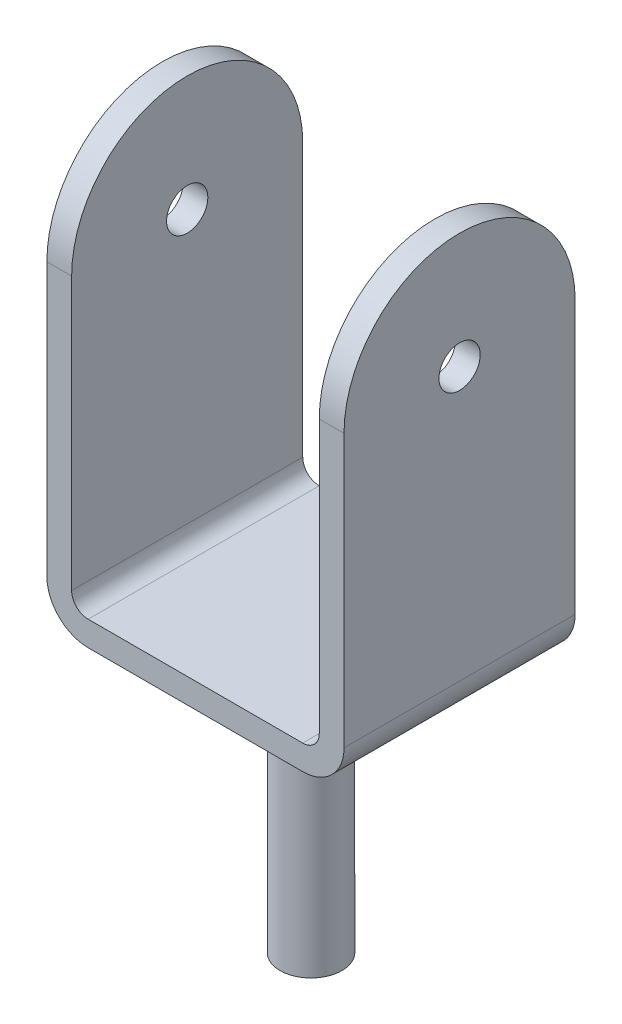
SolidWorks part; units mm, degrees
ref_plane "Front Plane" through (0, 0, 0) normal (0, 0, 1) x (1, 0, 0)
ref_plane "Top Plane" through (0, 0, 0) normal (0, 1, 0) x (1, 0, 0)
ref_plane "Right Plane" through (0, 0, 0) normal (1, 0, 0) x (0, 0, -1)
sketch "Sketch4" plane through (0, 0, 0) normal (0, 0, 1) x (1, 0, 0)
  line L0 (0, 0) -> (0, 149.0261) construction
  line L1 (-130, 0) -> (130, 0)
  line L2 (-180, 50) -> (-180, 380)
  line L3 (-180, 380) -> (-150, 380)
  line L4 (-150, 380) -> (-150, 50)
  line L5 (-130, 30) -> (130, 30)
  line L6 (150, 50) -> (150, 380)
  line L7 (150, 380) -> (180, 380)
  line L8 (180, 380) -> (180, 50)
  arc A0 (130, 0) -> (180, 50) centre (130, 50) ccw
  arc A1 (-130, 0) -> (-180, 50) centre (-130, 50) cw
  arc A2 (130, 30) -> (150, 50) centre (130, 50) ccw
  arc A3 (-150, 50) -> (-130, 30) centre (-130, 50) ccw
  point P13 (180, 0)
  point P16 (-180, 0)
  dimension "D5" = 50
  dimension "D6" = 20
  dimension "D1" = 30
  dimension "D2" = 360
  dimension "D3" = 380
  dimension "D4" = 30
extrude "Boss-Extrude2" add sketch "Sketch4" against normal blind 280
sketch "Sketch5" plane through (0, 0, 0) normal (1, 0, 0) x (0, 0, -1)
  line L0 (280, 380) -> (0, 380) construction
  circle A0 centre (140, 380) radius 140
  dimension "D1" = 280
extrude "Boss-Extrude3" add sketch "Sketch5" along normal blind 30 from surface starting at face at (150, 215, -140)
extrude "Boss-Extrude4" add sketch "Sketch5<2>" against normal blind 30 from surface starting at face at (-150, 215, -140)
sketch "Sketch5<2>" plane through (0, 0, 0) normal (1, 0, 0) x (0, 0, -1) same geometry as "Sketch5"
sketch "Sketch6" plane through (0, 0, 0) normal (1, 0, 0) x (0, 0, -1)
  circle A0 centre (140, 380) radius 25
  dimension "D1" = 50
extrude "Cut-Extrude1" cut sketch "Sketch6" against normal through all both and the other way through all
sketch "Sketch7" plane through (0, 0, 0) normal (0, 1, 0) x (1, 0, 0)
  line L0 (130, 0) -> (-130, 0) construction
  circle A0 centre (0, 140) radius 37.5
  point P2 (0, 0)
  dimension "D1" = 75
  dimension "D2" = 140
extrude "Boss-Extrude5" add sketch "Sketch7" against normal blind 325
